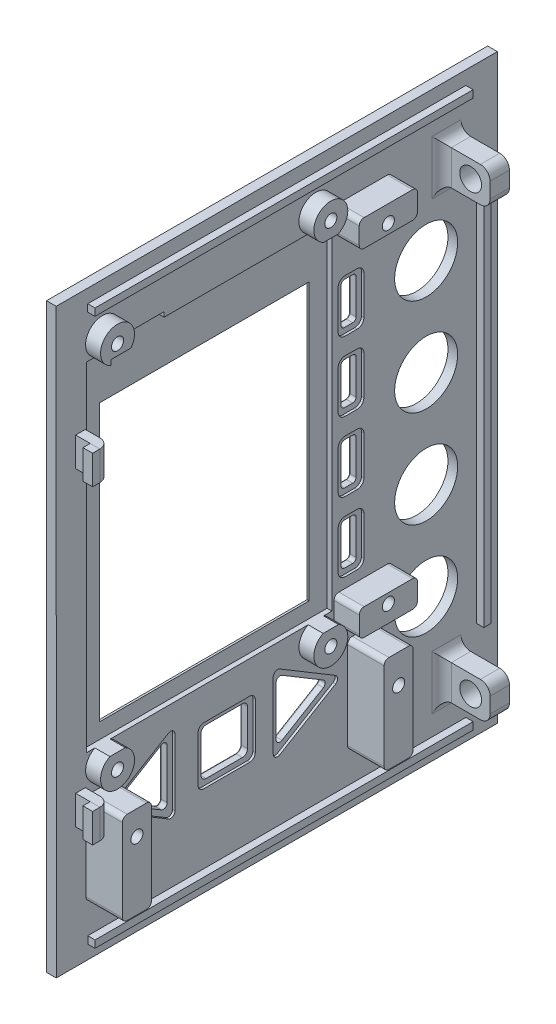
SolidWorks part; units mm, degrees
ref_plane "Front Plane" through (0, 0, 0) normal (0, 0, 1) x (1, 0, 0)
ref_plane "Top Plane" through (0, 0, 0) normal (0, 1, 0) x (1, 0, 0)
ref_plane "Right Plane" through (0, 0, 0) normal (1, 0, 0) x (0, 0, -1)
ref_plane "Plane2" through (-1175.048, -0.0877, 0) normal (-1, -0.0001, 0) x (0, 0, 1)
sketch "Sketch2" plane through (-1175.048, -0.0877, 0) normal (-1, -0.0001, 0) x (0, 0, 1)
  line L0 (-1289.195, -889.282) -> (-1289.195, -789.282) construction
  line L1 (-1204.195, -779.282) -> (-1295.195, -779.282)
  line L2 (-1204.195, -779.282) -> (-1204.195, -899.282)
  line L3 (-1204.195, -899.282) -> (-1295.195, -899.282)
  line L4 (-1295.195, -779.282) -> (-1295.195, -899.282)
  line L5 (-1289.195, -889.282) -> (-1287.685, -889.282) construction
  line L6 (-1289.195, -789.282) -> (-1287.685, -789.282) construction
  circle A0 centre (-1280.5, -869.282) radius 6.5
  circle A1 centre (-1280.5, -849.282) radius 6.5
  circle A2 centre (-1280.5, -829.282) radius 6.5
  circle A3 centre (-1280.5, -809.282) radius 6.5
  ellipse E0 centre (-1280.5, -869.282) end of major axis (-1280.4976, -868.632) minor radius 0.65 construction
  ellipse E1 centre (-1280.5, -849.282) end of major axis (-1280.4976, -848.632) minor radius 0.65 construction
  ellipse E2 centre (-1280.5, -829.282) end of major axis (-1280.4976, -828.632) minor radius 0.65 construction
  ellipse E3 centre (-1280.5, -809.282) end of major axis (-1280.4976, -808.632) minor radius 0.65 construction
  ellipse E4 centre (-1280.5, -869.282) end of major axis (-1280.4976, -868.632) minor radius 0.65
  ellipse E5 centre (-1280.5, -849.282) end of major axis (-1280.4976, -848.632) minor radius 0.65 construction
  ellipse E6 centre (-1280.5, -829.282) end of major axis (-1280.4976, -828.632) minor radius 0.65
  ellipse E7 centre (-1280.5, -809.282) end of major axis (-1280.4976, -808.632) minor radius 0.65
  dimension "D5" = 13
  dimension "D6" = 13
  dimension "D7" = 13
  dimension "D8" = 13
  dimension "D1" = 6
  dimension "D2" = 10
  dimension "D3" = 10
  dimension "D4" = 91
extrude "Boss-Extrude2" add sketch "Sketch2" along normal blind 2 contours L1 L4 L3 L2 A3 A2 A1 A0 region at (-1174.9854, -839.3697, -1248.1207)
sketch "Sketch3" plane through (-1177.048, -0.0879, 0) normal (-1, -0.0001, 0) x (0, 0, 1)
  line L12 (-1214.15, -858.982) -> (-1257.35, -858.982) construction
  line L13 (-1257.35, -858.982) -> (-1257.35, -802.002) construction
  line L14 (-1214.15, -802.002) -> (-1214.15, -858.982) construction
  line L15 (-1257.35, -802.002) -> (-1214.15, -802.002) construction
  line L16 (-1214.15, -858.982) -> (-1257.35, -858.982)
  line L17 (-1257.35, -858.982) -> (-1257.35, -802.002)
  line L18 (-1214.15, -802.002) -> (-1214.15, -858.982)
  line L19 (-1257.35, -802.002) -> (-1214.15, -802.002)
extrude "tft_cutout" cut sketch "Sketch3" against normal through all
sketch "tft_inset_cutout" plane through (-1175.048, -0.0877, 0) normal (1, 0.0001, 0) x (0, 0, -1)
  line L4 (1210.95, -792.861) -> (1210.95, -861.661) construction
  line L5 (1260.55, -792.861) -> (1210.95, -792.861) construction
  line L12 (1260.55, -861.661) -> (1260.55, -792.861) construction
  line L17 (1210.95, -861.661) -> (1260.55, -861.661) construction
  line L18 (1260.55, -861.661) -> (1260.55, -792.861) construction
  line L19 (1210.95, -861.661) -> (1260.55, -861.661) construction
  line L20 (1210.95, -792.861) -> (1210.95, -861.661) construction
  line L21 (1260.55, -792.861) -> (1210.95, -792.861) construction
  line L22 (1261.05, -792.361) -> (1210.45, -792.361)
  line L26 (1212.45, -792.861) -> (1226.45, -792.861)
  line L27 (1212.45, -792.861) -> (1212.45, -791.361)
  line L28 (1212.45, -791.361) -> (1226.45, -791.361)
  line L29 (1226.45, -792.861) -> (1226.45, -791.361)
  line L30 (1210.45, -792.361) -> (1210.45, -862.161)
  line L31 (1210.45, -862.161) -> (1261.05, -862.161)
  line L32 (1261.05, -862.161) -> (1261.05, -792.361)
  line M40 (1257.35, -858.982) -> (1214.15, -858.982)
  line M41 (1214.15, -858.982) -> (1214.15, -802.002)
  line M42 (1214.15, -802.002) -> (1257.35, -802.002)
  line M43 (1257.35, -802.002) -> (1257.35, -858.982)
  dimension "D3" = 1.5
  dimension "D4" = 0.5
  dimension "D1" = 14
  dimension "D2" = 1.5
extrude "Cut-Extrude2" cut sketch "tft_inset_cutout" against normal up to surface (1 mm away) contours L18 | L31 L32 L22 L29 L26 L27 L30 M43 M40 M41 M42 | L26 L29 L22 L27 | L22 L29 L28 L27 region at (-1174.9863, -827.3487, -1260.1879) region at (-1174.9889, -792.6987, -1219.45) region at (-1174.9889, -791.9487, -1219.45)
chamfer "Chamfer2" distance 1 angle 30 4 edges at (-1176.986, -830.5798, -1257.35) (-1176.9839, -859.0698, -1235.75) (-1176.986, -830.5798, -1214.15) (-1176.9882, -802.0898, -1235.75) first distance on face at (-1176.986, -830.5798, -1235.75)
sketch "Sketch6" plane through (-1175.048, -0.0877, 0) normal (1, 0.0001, 0) x (0, 0, -1)
  line L5 (1261.5, -864.9905) -> (1273.5, -864.9905)
  line L6 (1261.5, -864.9905) -> (1261.5, -859.4905)
  line L7 (1261.5, -859.4905) -> (1273.5, -859.4905)
  line L8 (1261.5, -864.9905) -> (1273.5, -864.9905)
  line L9 (1273.5, -864.9905) -> (1273.5, -789.9905)
  line L10 (1273.5, -789.9905) -> (1261.5, -789.9905)
  line L11 (1261.5, -789.9905) -> (1261.5, -864.9905)
  line L12 (1261.5, -864.9905) -> (1273.5, -864.9905) construction
  line L13 (1273.5, -864.9905) -> (1273.5, -789.9905) construction
  line L14 (1273.5, -789.9905) -> (1261.5, -789.9905) construction
  line L15 (1261.5, -789.9905) -> (1261.5, -864.9905) construction
  line L16 (1273.5, -864.9905) -> (1273.5, -859.4905)
  line L17 (1261.5, -789.9905) -> (1273.5, -789.9905)
  line L18 (1261.5, -789.9905) -> (1261.5, -795.4905)
  line L19 (1261.5, -795.4905) -> (1273.5, -795.4905)
  line L20 (1273.5, -789.9905) -> (1273.5, -795.4905)
  circle A0 centre (1267.5, -861.4905) radius 1.25 construction
  circle A1 centre (1267.5, -861.4905) radius 1.25 construction
  circle A2 centre (1267.5, -861.4905) radius 1.25
  circle A3 centre (1267.5, -793.4905) radius 1.25 construction
  circle A4 centre (1267.5, -793.4905) radius 1.25 construction
  circle A5 centre (1267.5, -793.4905) radius 1.25
  dimension "D2" = 2.5
  dimension "D4" = 2.5
  dimension "D3" = 2
  dimension "D5" = 2
extrude "menu_standoffs" add sketch "Sketch6" along normal up to surface (5.203 mm away)
fillet "Fillet1" radius 1 8 edges at (-1172.3871, -795.578, -1261.5) (-1172.3871, -795.578, -1273.5) (-1172.3875, -790.078, -1273.5) (-1172.3875, -790.078, -1261.5) (-1172.3824, -859.578, -1273.5) (-1172.3824, -859.578, -1261.5) (-1172.382, -865.078, -1261.5) (-1172.382, -865.078, -1273.5)
sketch "Sketch7" plane through (-1169.845, -0.0873, 0) normal (1, 0.0001, 0) x (0, 0, -1)
  circle A0 centre (1267.5, -861.4905) radius 1.25 construction
  circle A1 centre (1267.5, -793.4905) radius 1.25 construction
  circle A2 centre (1267.5, -861.4905) radius 1.25
  circle A3 centre (1267.5, -793.4905) radius 1.25
extrude "menu_standoff_holes" [suppressed] cut sketch "Sketch7" against normal blind 5 contours A2
sketch "Sketch8" plane through (-1175.048, -0.0877, 0) normal (1, 0.0001, 0) x (0, 0, -1)
  circle A0 centre (1213.75, -865.282) radius 1.55 construction
  circle A1 centre (1257.75, -865.282) radius 1.55 construction
  circle A2 centre (1257.75, -789.202) radius 1.55 construction
  circle A3 centre (1213.75, -789.2023) radius 1.55 construction
  circle A4 centre (1213.75, -865.282) radius 1.55 construction
  circle A5 centre (1257.75, -865.282) radius 1.55 construction
  circle A6 centre (1257.75, -789.202) radius 1.55 construction
  circle A7 centre (1213.75, -789.2023) radius 1.55 construction
  circle A8 centre (1213.75, -789.2023) radius 3.5
  circle A9 centre (1257.75, -789.202) radius 3.5
  circle A10 centre (1257.75, -865.282) radius 3.5
  circle A11 centre (1213.75, -865.282) radius 3.5
  circle A12 centre (1213.75, -789.2023) radius 1.25
  circle A13 centre (1213.75, -865.282) radius 1.25
  circle A14 centre (1257.75, -865.282) radius 1.25
  circle A15 centre (1257.75, -789.202) radius 1.25
  dimension "D2" = 2.5
  dimension "D1" = 7
extrude "TFT_standoffs" add sketch "Sketch8" along normal up to surface (3.09 mm away)
sketch "Sketch9" plane through (-1175.048, -0.0877, 0) normal (1, 0.0001, 0) x (0, 0, -1)
  circle A0 centre (1213.75, -789.2023) radius 1.25 construction
  circle A1 centre (1213.75, -865.282) radius 1.25 construction
  circle A2 centre (1257.75, -865.282) radius 1.25 construction
  circle A3 centre (1257.75, -789.202) radius 1.25 construction
  circle A4 centre (1213.75, -789.2023) radius 1.25
  circle A5 centre (1213.75, -865.282) radius 1.25
  circle A6 centre (1257.75, -865.282) radius 1.25
  circle A7 centre (1257.75, -789.202) radius 1.25
extrude "TFT_standoff_holes" cut sketch "Sketch9" against normal offset from surface (1 mm away) 1 up to face at (-1176.986, -830.5798, -1235.75)
extrude "Cut-Extrude5" cut sketch "Sketch5<3>" along normal through all contours L31 L32 L22 L29 L26 L27 L30 M43 M40 M41 M42 | L22 L29 L28 L27 | L26 L29 L22 L27 region at (-1174.9863, -827.3487, -1260.1879) region at (-1174.9889, -792.6987, -1219.45) region at (-1174.9889, -791.9487, -1219.45)
sketch "Sketch5<3>" plane through (-1175.048, -0.0877, 0) normal (1, 0.0001, 0) x (0, 0, -1) same geometry as "tft_inset_cutout"
sketch "Sketch10" plane through (-1175.048, -0.0877, 0) normal (1, 0.0001, 0) x (0, 0, -1)
  line L0 (1267.2535, -804.997) -> (1267.2535, -812.997) construction
  line L1 (1266.2535, -813.997) -> (1263.7535, -813.997) construction
  line L2 (1262.7535, -812.997) -> (1262.7535, -804.997) construction
  line L3 (1263.7535, -803.997) -> (1266.2535, -803.997) construction
  line L4 (1267.2535, -804.997) -> (1267.2535, -812.997) construction
  line L5 (1266.2535, -813.997) -> (1263.7535, -813.997) construction
  line L6 (1262.7535, -812.997) -> (1262.7535, -804.997) construction
  line L7 (1263.7535, -803.997) -> (1266.2535, -803.997) construction
  line L8 (1267.6535, -804.997) -> (1267.6535, -812.997)
  line L9 (1266.2535, -814.397) -> (1263.7535, -814.397)
  line L10 (1262.3535, -812.997) -> (1262.3535, -804.997)
  line L11 (1263.7535, -803.597) -> (1266.2535, -803.597)
  line L12 (1267.6535, -819.327) -> (1267.6535, -827.327)
  line L13 (1266.2535, -828.727) -> (1263.7535, -828.727)
  line L14 (1262.3535, -827.327) -> (1262.3535, -819.327)
  line L15 (1263.7535, -817.927) -> (1266.2535, -817.927)
  line L16 (1267.2535, -819.327) -> (1267.2535, -827.327) construction
  line L17 (1266.2535, -828.327) -> (1263.7535, -828.327) construction
  line L18 (1262.7535, -827.327) -> (1262.7535, -819.327) construction
  line L19 (1263.7535, -818.327) -> (1266.2535, -818.327) construction
  line L20 (1267.6535, -833.657) -> (1267.6535, -841.657)
  line L21 (1266.2535, -843.057) -> (1263.7535, -843.057)
  line L22 (1262.3535, -841.657) -> (1262.3535, -833.657)
  line L23 (1263.7535, -832.257) -> (1266.2535, -832.257)
  line L24 (1267.2535, -833.657) -> (1267.2535, -841.657) construction
  line L25 (1266.2535, -842.657) -> (1263.7535, -842.657) construction
  line L26 (1262.7535, -841.657) -> (1262.7535, -833.657) construction
  line L27 (1263.7535, -832.657) -> (1266.2535, -832.657) construction
  line L28 (1267.6535, -847.987) -> (1267.6535, -855.987)
  line L29 (1266.2535, -857.387) -> (1263.7535, -857.387)
  line L30 (1262.3535, -855.987) -> (1262.3535, -847.987)
  line L31 (1263.7535, -846.587) -> (1266.2535, -846.587)
  line L32 (1267.2535, -847.987) -> (1267.2535, -855.987) construction
  line L33 (1266.2535, -856.987) -> (1263.7535, -856.987) construction
  line L34 (1262.7535, -855.987) -> (1262.7535, -847.987) construction
  line L35 (1263.7535, -846.987) -> (1266.2535, -846.987) construction
  arc A0 (1267.2535, -804.997) -> (1266.2535, -803.997) centre (1266.2535, -804.997) ccw construction
  arc A1 (1266.2535, -813.997) -> (1267.2535, -812.997) centre (1266.2535, -812.997) ccw construction
  arc A2 (1262.7535, -812.997) -> (1263.7535, -813.997) centre (1263.7535, -812.997) ccw construction
  arc A3 (1263.7535, -803.997) -> (1262.7535, -804.997) centre (1263.7535, -804.997) ccw construction
  arc A4 (1267.2535, -804.997) -> (1266.2535, -803.997) centre (1266.2535, -804.997) ccw construction
  arc A5 (1266.2535, -813.997) -> (1267.2535, -812.997) centre (1266.2535, -812.997) ccw construction
  arc A6 (1262.7535, -812.997) -> (1263.7535, -813.997) centre (1263.7535, -812.997) ccw construction
  arc A7 (1263.7535, -803.997) -> (1262.7535, -804.997) centre (1263.7535, -804.997) ccw construction
  arc A8 (1266.2535, -814.397) -> (1267.6535, -812.997) centre (1266.2535, -812.997) ccw
  arc A9 (1262.3535, -812.997) -> (1263.7535, -814.397) centre (1263.7535, -812.997) ccw
  arc A10 (1263.7535, -803.597) -> (1262.3535, -804.997) centre (1263.7535, -804.997) ccw
  arc A11 (1267.6535, -804.997) -> (1266.2535, -803.597) centre (1266.2535, -804.997) ccw
  arc A12 (1266.2535, -828.727) -> (1267.6535, -827.327) centre (1266.2535, -827.327) ccw
  arc A13 (1262.3535, -827.327) -> (1263.7535, -828.727) centre (1263.7535, -827.327) ccw
  arc A14 (1263.7535, -817.927) -> (1262.3535, -819.327) centre (1263.7535, -819.327) ccw
  arc A15 (1267.6535, -819.327) -> (1266.2535, -817.927) centre (1266.2535, -819.327) ccw
  arc A16 (1267.2535, -819.327) -> (1266.2535, -818.327) centre (1266.2535, -819.327) ccw construction
  arc A17 (1266.2535, -828.327) -> (1267.2535, -827.327) centre (1266.2535, -827.327) ccw construction
  arc A18 (1262.7535, -827.327) -> (1263.7535, -828.327) centre (1263.7535, -827.327) ccw construction
  arc A19 (1263.7535, -818.327) -> (1262.7535, -819.327) centre (1263.7535, -819.327) ccw construction
  arc A20 (1266.2535, -843.057) -> (1267.6535, -841.657) centre (1266.2535, -841.657) ccw
  arc A21 (1262.3535, -841.657) -> (1263.7535, -843.057) centre (1263.7535, -841.657) ccw
  arc A22 (1263.7535, -832.257) -> (1262.3535, -833.657) centre (1263.7535, -833.657) ccw
  arc A23 (1267.6535, -833.657) -> (1266.2535, -832.257) centre (1266.2535, -833.657) ccw
  arc A24 (1267.2535, -833.657) -> (1266.2535, -832.657) centre (1266.2535, -833.657) ccw construction
  arc A25 (1266.2535, -842.657) -> (1267.2535, -841.657) centre (1266.2535, -841.657) ccw construction
  arc A26 (1262.7535, -841.657) -> (1263.7535, -842.657) centre (1263.7535, -841.657) ccw construction
  arc A27 (1263.7535, -832.657) -> (1262.7535, -833.657) centre (1263.7535, -833.657) ccw construction
  arc A28 (1266.2535, -857.387) -> (1267.6535, -855.987) centre (1266.2535, -855.987) ccw
  arc A29 (1262.3535, -855.987) -> (1263.7535, -857.387) centre (1263.7535, -855.987) ccw
  arc A30 (1263.7535, -846.587) -> (1262.3535, -847.987) centre (1263.7535, -847.987) ccw
  arc A31 (1267.6535, -847.987) -> (1266.2535, -846.587) centre (1266.2535, -847.987) ccw
  arc A32 (1267.2535, -847.987) -> (1266.2535, -846.987) centre (1266.2535, -847.987) ccw construction
  arc A33 (1266.2535, -856.987) -> (1267.2535, -855.987) centre (1266.2535, -855.987) ccw construction
  arc A34 (1262.7535, -855.987) -> (1263.7535, -856.987) centre (1263.7535, -855.987) ccw construction
  arc A35 (1263.7535, -846.987) -> (1262.7535, -847.987) centre (1263.7535, -847.987) ccw construction
  dimension "D1" = 0.4
  dimension "D2" = 4
extrude "menu_panel_inset" cut sketch "Sketch10" against normal offset from surface 1.5 and the other way through all up to face at (-1176.986, -830.5798, -1235.75)
sketch "Sketch11" plane through (-1177.048, -0.0879, 0) normal (-1, -0.0001, 0) x (0, 0, 1)
  line L0 (-1265.8535, -812.997) -> (-1264.1535, -812.997) construction
  line L1 (-1266.2535, -805.397) -> (-1266.2535, -812.597) construction
  line L2 (-1265.8535, -804.997) -> (-1264.1535, -804.997) construction
  line L3 (-1263.7535, -805.397) -> (-1263.7535, -812.597) construction
  line L4 (-1265.8535, -812.997) -> (-1264.1535, -812.997) construction
  line L5 (-1266.2535, -805.397) -> (-1266.2535, -812.597) construction
  line L6 (-1265.8535, -804.997) -> (-1264.1535, -804.997) construction
  line L7 (-1263.7535, -805.397) -> (-1263.7535, -812.597) construction
  line L8 (-1263.4535, -805.397) -> (-1263.4535, -812.597)
  line L9 (-1265.8535, -813.297) -> (-1264.1535, -813.297)
  line L10 (-1266.5535, -805.397) -> (-1266.5535, -812.597)
  line L11 (-1265.8535, -804.697) -> (-1264.1535, -804.697)
  line L12 (-1263.4535, -819.727) -> (-1263.4535, -826.927)
  line L13 (-1265.8535, -827.627) -> (-1264.1535, -827.627)
  line L14 (-1266.5535, -819.727) -> (-1266.5535, -826.927)
  line L15 (-1265.8535, -819.027) -> (-1264.1535, -819.027)
  line L16 (-1265.8535, -827.327) -> (-1264.1535, -827.327) construction
  line L17 (-1266.2535, -819.727) -> (-1266.2535, -826.927) construction
  line L18 (-1265.8535, -819.327) -> (-1264.1535, -819.327) construction
  line L19 (-1263.7535, -819.727) -> (-1263.7535, -826.927) construction
  line L20 (-1263.4535, -834.057) -> (-1263.4535, -841.257)
  line L21 (-1265.8535, -841.957) -> (-1264.1535, -841.957)
  line L22 (-1266.5535, -834.057) -> (-1266.5535, -841.257)
  line L23 (-1265.8535, -833.357) -> (-1264.1535, -833.357)
  line L24 (-1265.8535, -841.657) -> (-1264.1535, -841.657) construction
  line L25 (-1266.2535, -834.057) -> (-1266.2535, -841.257) construction
  line L26 (-1265.8535, -833.657) -> (-1264.1535, -833.657) construction
  line L27 (-1263.7535, -834.057) -> (-1263.7535, -841.257) construction
  line L28 (-1263.4535, -848.387) -> (-1263.4535, -855.587)
  line L29 (-1265.8535, -856.287) -> (-1264.1535, -856.287)
  line L30 (-1266.5535, -848.387) -> (-1266.5535, -855.587)
  line L31 (-1265.8535, -847.687) -> (-1264.1535, -847.687)
  line L32 (-1265.8535, -855.987) -> (-1264.1535, -855.987) construction
  line L33 (-1266.2535, -848.387) -> (-1266.2535, -855.587) construction
  line L34 (-1265.8535, -847.987) -> (-1264.1535, -847.987) construction
  line L35 (-1263.7535, -848.387) -> (-1263.7535, -855.587) construction
  arc A0 (-1264.1535, -812.997) -> (-1263.7535, -812.597) centre (-1264.1535, -812.597) ccw construction
  arc A1 (-1266.2535, -812.597) -> (-1265.8535, -812.997) centre (-1265.8535, -812.597) ccw construction
  arc A2 (-1265.8535, -804.997) -> (-1266.2535, -805.397) centre (-1265.8535, -805.397) ccw construction
  arc A3 (-1263.7535, -805.397) -> (-1264.1535, -804.997) centre (-1264.1535, -805.397) ccw construction
  arc A4 (-1264.1535, -812.997) -> (-1263.7535, -812.597) centre (-1264.1535, -812.597) ccw construction
  arc A5 (-1266.2535, -812.597) -> (-1265.8535, -812.997) centre (-1265.8535, -812.597) ccw construction
  arc A6 (-1265.8535, -804.997) -> (-1266.2535, -805.397) centre (-1265.8535, -805.397) ccw construction
  arc A7 (-1263.7535, -805.397) -> (-1264.1535, -804.997) centre (-1264.1535, -805.397) ccw construction
  arc A8 (-1264.1535, -813.297) -> (-1263.4535, -812.597) centre (-1264.1535, -812.597) ccw
  arc A9 (-1266.5535, -812.597) -> (-1265.8535, -813.297) centre (-1265.8535, -812.597) ccw
  arc A10 (-1265.8535, -804.697) -> (-1266.5535, -805.397) centre (-1265.8535, -805.397) ccw
  arc A11 (-1263.4535, -805.397) -> (-1264.1535, -804.697) centre (-1264.1535, -805.397) ccw
  arc A12 (-1264.1535, -827.627) -> (-1263.4535, -826.927) centre (-1264.1535, -826.927) ccw
  arc A13 (-1266.5535, -826.927) -> (-1265.8535, -827.627) centre (-1265.8535, -826.927) ccw
  arc A14 (-1265.8535, -819.027) -> (-1266.5535, -819.727) centre (-1265.8535, -819.727) ccw
  arc A15 (-1263.4535, -819.727) -> (-1264.1535, -819.027) centre (-1264.1535, -819.727) ccw
  arc A16 (-1264.1535, -827.327) -> (-1263.7535, -826.927) centre (-1264.1535, -826.927) ccw construction
  arc A17 (-1266.2535, -826.927) -> (-1265.8535, -827.327) centre (-1265.8535, -826.927) ccw construction
  arc A18 (-1265.8535, -819.327) -> (-1266.2535, -819.727) centre (-1265.8535, -819.727) ccw construction
  arc A19 (-1263.7535, -819.727) -> (-1264.1535, -819.327) centre (-1264.1535, -819.727) ccw construction
  arc A20 (-1264.1535, -841.957) -> (-1263.4535, -841.257) centre (-1264.1535, -841.257) ccw
  arc A21 (-1266.5535, -841.257) -> (-1265.8535, -841.957) centre (-1265.8535, -841.257) ccw
  arc A22 (-1265.8535, -833.357) -> (-1266.5535, -834.057) centre (-1265.8535, -834.057) ccw
  arc A23 (-1263.4535, -834.057) -> (-1264.1535, -833.357) centre (-1264.1535, -834.057) ccw
  arc A24 (-1264.1535, -841.657) -> (-1263.7535, -841.257) centre (-1264.1535, -841.257) ccw construction
  arc A25 (-1266.2535, -841.257) -> (-1265.8535, -841.657) centre (-1265.8535, -841.257) ccw construction
  arc A26 (-1265.8535, -833.657) -> (-1266.2535, -834.057) centre (-1265.8535, -834.057) ccw construction
  arc A27 (-1263.7535, -834.057) -> (-1264.1535, -833.657) centre (-1264.1535, -834.057) ccw construction
  arc A28 (-1264.1535, -856.287) -> (-1263.4535, -855.587) centre (-1264.1535, -855.587) ccw
  arc A29 (-1266.5535, -855.587) -> (-1265.8535, -856.287) centre (-1265.8535, -855.587) ccw
  arc A30 (-1265.8535, -847.687) -> (-1266.5535, -848.387) centre (-1265.8535, -848.387) ccw
  arc A31 (-1263.4535, -848.387) -> (-1264.1535, -847.687) centre (-1264.1535, -848.387) ccw
  arc A32 (-1264.1535, -855.987) -> (-1263.7535, -855.587) centre (-1264.1535, -855.587) ccw construction
  arc A33 (-1266.2535, -855.587) -> (-1265.8535, -855.987) centre (-1265.8535, -855.587) ccw construction
  arc A34 (-1265.8535, -847.987) -> (-1266.2535, -848.387) centre (-1265.8535, -848.387) ccw construction
  arc A35 (-1263.7535, -848.387) -> (-1264.1535, -847.987) centre (-1264.1535, -848.387) ccw construction
  dimension "D1" = 0.3
  dimension "D2" = 4
extrude "menu_panel_cutout" cut sketch "Sketch11" against normal through all
fillet "Fillet2" radius 0.25 32 edges at (-1176.9876, -809.0848, -1263.4535) (-1176.9873, -813.1798, -1263.6586) (-1176.9873, -813.3848, -1265.0035) (-1176.9873, -813.1798, -1266.3485) (-1176.9876, -809.0848, -1266.5535) (-1176.9879, -804.9899, -1266.3485) (-1176.988, -804.7848, -1265.0035) (-1176.9862, -827.7148, -1265.0035) (-1176.9863, -827.5098, -1266.3485) (-1176.9866, -823.4148, -1266.5535) (-1176.9869, -819.3199, -1266.3485) (-1176.9869, -819.1148, -1265.0035) (-1176.9869, -819.3199, -1263.6586) (-1176.9866, -823.4148, -1263.4535) (-1176.9852, -842.0448, -1265.0035) (-1176.9852, -841.8398, -1266.3485) (-1176.9855, -837.7448, -1266.5535) (-1176.9858, -833.6499, -1266.3485) (-1176.9858, -833.4448, -1265.0035) (-1176.9858, -833.6499, -1263.6586) (-1176.9855, -837.7448, -1263.4535) (-1176.9844, -852.0748, -1263.4535) (-1176.9841, -856.1698, -1263.6586) (-1176.9841, -856.3748, -1265.0035) (-1176.9841, -856.1698, -1266.3485) (-1176.9844, -852.0748, -1266.5535) (-1176.9847, -847.9799, -1266.3485) (-1176.9847, -847.7748, -1265.0035) (-1176.9879, -804.9899, -1263.6586) (-1176.9863, -827.5098, -1263.6586) (-1176.9852, -841.8398, -1263.6586) (-1176.9847, -847.9799, -1263.6586)
sketch "Sketch12" plane through (-1175.048, -0.0877, 0) normal (1, 0.0001, 0) x (0, 0, -1)
  line L0 (1270.2797, -888.782) -> (1210.2797, -888.782) construction
  line L1 (1270.2797, -868.782) -> (1264.2797, -868.782)
  line L2 (1270.2797, -868.782) -> (1270.2797, -888.782)
  line L3 (1270.2797, -888.782) -> (1264.2797, -888.782)
  line L4 (1264.2797, -868.782) -> (1264.2797, -888.782)
  line L6 (1210.2797, -888.782) -> (1216.2797, -888.782)
  line L7 (1210.2797, -888.782) -> (1210.2797, -869.782)
  line L8 (1210.2797, -869.782) -> (1216.2797, -869.782)
  line L9 (1216.2797, -888.782) -> (1216.2797, -869.782)
  line L10 (1210.2797, -868.782) -> (1270.2797, -868.782) construction
  circle A0 centre (1267.2797, -874.782) radius 1.25
  circle A1 centre (1213.2797, -874.782) radius 1.25
  dimension "D1" = 6
  dimension "D2" = 2.5
  dimension "D4" = 2.5
  dimension "D3" = 6
  dimension "D5" = 1
extrude "selector_standoffs" add sketch "Sketch12" along normal up to surface (7.55 mm away) contours L6 L9 L8 L7 A1 | L1 L4 L3 L2 A0 region at (-1174.9824, -879.0403, -1267.2797) region at (-1174.9824, -879.5722, -1213.2797)
fillet "Fillet3" radius 1 8 edges at (-1171.2067, -888.8694, -1270.2797) (-1171.2082, -868.8694, -1270.2797) (-1171.2082, -868.8694, -1264.2797) (-1171.2067, -888.8694, -1264.2797) (-1171.2067, -888.8694, -1216.2797) (-1171.2067, -888.8694, -1210.2797) (-1171.2081, -869.8694, -1210.2797) (-1171.2081, -869.8694, -1216.2797)
sketch "Sketch13" plane through (-1175.048, -0.0877, 0) normal (1, 0.0001, 0) x (0, 0, -1)
  line L0 (1218.0014, -875.2178) -> (1226.5296, -880.3347) construction
  line L1 (1227.2868, -879.906) -> (1227.2868, -869.6722) construction
  line L2 (1226.5296, -869.2434) -> (1218.0014, -874.3603) construction
  line L3 (1234.85, -871.0391) -> (1234.85, -878.5391) construction
  line L4 (1235.6, -879.2891) -> (1243.1, -879.2891) construction
  line L5 (1243.1, -870.2891) -> (1235.6, -870.2891) construction
  line L6 (1243.85, -878.5391) -> (1243.85, -871.0391) construction
  line L7 (1259.6354, -874.3603) -> (1251.1072, -869.2434) construction
  line L8 (1250.35, -869.6722) -> (1250.35, -879.906) construction
  line L9 (1251.1072, -880.3347) -> (1259.6354, -875.2178) construction
  line L10 (1218.0014, -875.2178) -> (1226.5296, -880.3347) construction
  line L11 (1227.2868, -879.906) -> (1227.2868, -869.6722) construction
  line L12 (1226.5296, -869.2434) -> (1218.0014, -874.3603) construction
  line L13 (1234.85, -871.0391) -> (1234.85, -878.5391) construction
  line L14 (1235.6, -879.2891) -> (1243.1, -879.2891) construction
  line L15 (1243.1, -870.2891) -> (1235.6, -870.2891) construction
  line L16 (1243.85, -878.5391) -> (1243.85, -871.0391) construction
  line L17 (1259.6354, -874.3603) -> (1251.1072, -869.2434) construction
  line L18 (1250.35, -869.6722) -> (1250.35, -879.906) construction
  line L19 (1251.1072, -880.3347) -> (1259.6354, -875.2178) construction
  line L20 (1217.847, -875.4751) -> (1226.3752, -880.592)
  line L21 (1227.5868, -879.906) -> (1227.5868, -869.6722)
  line L22 (1226.3752, -868.9862) -> (1217.847, -874.1031)
  line L23 (1234.55, -871.0391) -> (1234.55, -878.5391)
  line L24 (1235.6, -879.5891) -> (1243.1, -879.5891)
  line L25 (1244.15, -878.5391) -> (1244.15, -871.0391)
  line L26 (1243.1, -869.9891) -> (1235.6, -869.9891)
  line L27 (1259.7898, -874.1031) -> (1251.2616, -868.9862)
  line L28 (1250.05, -869.6722) -> (1250.05, -879.906)
  line L29 (1251.2616, -880.592) -> (1259.7898, -875.4751)
  arc A0 (1218.0014, -874.3603) -> (1218.0014, -875.2178) centre (1218.2586, -874.7891) ccw construction
  arc A1 (1226.5296, -880.3347) -> (1227.2868, -879.906) centre (1226.7868, -879.906) ccw construction
  arc A2 (1227.2868, -869.6722) -> (1226.5296, -869.2434) centre (1226.7868, -869.6722) ccw construction
  arc A3 (1235.6, -870.2891) -> (1234.85, -871.0391) centre (1235.6, -871.0391) ccw construction
  arc A4 (1234.85, -878.5391) -> (1235.6, -879.2891) centre (1235.6, -878.5391) ccw construction
  arc A5 (1243.1, -879.2891) -> (1243.85, -878.5391) centre (1243.1, -878.5391) ccw construction
  arc A6 (1243.85, -871.0391) -> (1243.1, -870.2891) centre (1243.1, -871.0391) ccw construction
  arc A7 (1259.6354, -875.2178) -> (1259.6354, -874.3603) centre (1259.3782, -874.7891) ccw construction
  arc A8 (1251.1072, -869.2434) -> (1250.35, -869.6722) centre (1250.85, -869.6722) ccw construction
  arc A9 (1250.35, -879.906) -> (1251.1072, -880.3347) centre (1250.85, -879.906) ccw construction
  arc A10 (1218.0014, -874.3603) -> (1218.0014, -875.2178) centre (1218.2586, -874.7891) ccw construction
  arc A11 (1226.5296, -880.3347) -> (1227.2868, -879.906) centre (1226.7868, -879.906) ccw construction
  arc A12 (1227.2868, -869.6722) -> (1226.5296, -869.2434) centre (1226.7868, -869.6722) ccw construction
  arc A13 (1235.6, -870.2891) -> (1234.85, -871.0391) centre (1235.6, -871.0391) ccw construction
  arc A14 (1234.85, -878.5391) -> (1235.6, -879.2891) centre (1235.6, -878.5391) ccw construction
  arc A15 (1243.1, -879.2891) -> (1243.85, -878.5391) centre (1243.1, -878.5391) ccw construction
  arc A16 (1243.85, -871.0391) -> (1243.1, -870.2891) centre (1243.1, -871.0391) ccw construction
  arc A17 (1259.6354, -875.2178) -> (1259.6354, -874.3603) centre (1259.3782, -874.7891) ccw construction
  arc A18 (1251.1072, -869.2434) -> (1250.35, -869.6722) centre (1250.85, -869.6722) ccw construction
  arc A19 (1250.35, -879.906) -> (1251.1072, -880.3347) centre (1250.85, -879.906) ccw construction
  arc A20 (1226.3752, -880.592) -> (1227.5868, -879.906) centre (1226.7868, -879.906) ccw
  arc A21 (1227.5868, -869.6722) -> (1226.3752, -868.9862) centre (1226.7868, -869.6722) ccw
  arc A22 (1217.847, -874.1031) -> (1217.847, -875.4751) centre (1218.2586, -874.7891) ccw
  arc A23 (1234.55, -878.5391) -> (1235.6, -879.5891) centre (1235.6, -878.5391) ccw
  arc A24 (1243.1, -879.5891) -> (1244.15, -878.5391) centre (1243.1, -878.5391) ccw
  arc A25 (1244.15, -871.0391) -> (1243.1, -869.9891) centre (1243.1, -871.0391) ccw
  arc A26 (1235.6, -869.9891) -> (1234.55, -871.0391) centre (1235.6, -871.0391) ccw
  arc A27 (1251.2616, -868.9862) -> (1250.05, -869.6722) centre (1250.85, -869.6722) ccw
  arc A28 (1250.05, -879.906) -> (1251.2616, -880.592) centre (1250.85, -879.906) ccw
  arc A29 (1259.7898, -875.4751) -> (1259.7898, -874.1031) centre (1259.3782, -874.7891) ccw
  dimension "D1" = 0.3
  dimension "D2" = 0.3
  dimension "D3" = 0.3
extrude "selector_cutout" cut sketch "Sketch13" against normal through all
fillet "Fillet4" radius 0.25 20 edges at (-1176.9824, -879.6769, -1239.35) (-1176.9824, -879.3694, -1234.8575) (-1176.9827, -874.8769, -1234.55) (-1176.9831, -870.3845, -1234.8575) (-1176.9831, -870.0769, -1239.35) (-1176.9831, -870.3845, -1243.8424) (-1176.9827, -874.8769, -1244.15) (-1176.9832, -869.0639, -1250.4558) (-1176.983, -871.6325, -1255.5257) (-1176.9827, -874.8769, -1260.1782) (-1176.9825, -878.1214, -1255.5257) (-1176.9823, -880.69, -1250.4558) (-1176.9824, -879.3694, -1243.8424) (-1176.9827, -874.8769, -1250.05) (-1176.9825, -878.1214, -1222.1111) (-1176.9827, -874.8769, -1217.4586) (-1176.983, -871.6325, -1222.1111) (-1176.9832, -869.0639, -1227.181) (-1176.9827, -874.8769, -1227.5868) (-1176.9823, -880.69, -1227.181)
sketch "Sketch17" plane through (-1175.048, -0.0877, 0) normal (1, 0.0001, 0) x (0, 0, -1)
  line L18 (1220.3082, -871.8101) -> (1216.0577, -874.3603) construction
  line L19 (1216.0577, -875.2178) -> (1220.3082, -877.7681) construction
  line L20 (1220.1868, -877.5537) -> (1220.1868, -872.0244) construction
  line L21 (1228.2868, -881.6722) -> (1228.2868, -867.906) construction
  line L22 (1227.5296, -867.4772) -> (1220.4505, -871.7247) construction
  line L23 (1220.5791, -871.6891) -> (1226.1368, -871.6891) construction
  line L24 (1226.3868, -871.9391) -> (1226.3868, -877.6391) construction
  line L25 (1226.1368, -877.8891) -> (1220.5791, -877.8891) construction
  line L26 (1220.4505, -877.8535) -> (1227.5296, -882.1009) construction
  line L27 (1220.3082, -871.8101) -> (1216.0577, -874.3603) construction
  line L28 (1216.0577, -875.2178) -> (1220.3082, -877.7681) construction
  line L29 (1220.1868, -877.5537) -> (1220.1868, -872.0244) construction
  line L30 (1228.2868, -881.6722) -> (1228.2868, -867.906) construction
  line L31 (1257.3286, -877.7681) -> (1261.5791, -875.2178) construction
  line L32 (1261.5791, -874.3603) -> (1257.3286, -871.8101) construction
  line L33 (1257.45, -872.0244) -> (1257.45, -877.5537) construction
  line L34 (1249.35, -867.906) -> (1249.35, -881.6722) construction
  line L35 (1250.1072, -882.1009) -> (1257.1863, -877.8535) construction
  line L36 (1257.0577, -877.8891) -> (1251.5, -877.8891) construction
  line L37 (1251.25, -877.6391) -> (1251.25, -871.9391) construction
  line L38 (1251.5, -871.6891) -> (1257.0577, -871.6891) construction
  line L39 (1257.1863, -871.7247) -> (1250.1072, -867.4772) construction
  line L40 (1233.85, -870.0391) -> (1233.85, -879.5391) construction
  line L41 (1234.6, -880.2891) -> (1244.1, -880.2891) construction
  line L42 (1244.85, -879.5391) -> (1244.85, -870.0391) construction
  line L43 (1244.1, -869.2891) -> (1234.6, -869.2891) construction
  line L44 (1257.3286, -877.7681) -> (1261.5791, -875.2178) construction
  line L45 (1261.5791, -874.3603) -> (1257.3286, -871.8101) construction
  line L46 (1257.45, -872.0244) -> (1257.45, -877.5537) construction
  line L47 (1249.35, -867.906) -> (1249.35, -881.6722) construction
  line L48 (1250.1072, -882.1009) -> (1257.1863, -877.8535) construction
  line L49 (1257.0577, -877.8891) -> (1251.5, -877.8891) construction
  line L50 (1251.25, -877.6391) -> (1251.25, -871.9391) construction
  line L51 (1251.5, -871.6891) -> (1257.0577, -871.6891) construction
  line L52 (1257.1863, -871.7247) -> (1250.1072, -867.4772) construction
  line L53 (1233.85, -870.0391) -> (1233.85, -879.5391) construction
  line L54 (1234.6, -880.2891) -> (1244.1, -880.2891) construction
  line L55 (1244.85, -879.5391) -> (1244.85, -870.0391) construction
  line L56 (1244.1, -869.2891) -> (1234.6, -869.2891) construction
  line L57 (1257.1863, -877.8535) -> (1257.3286, -877.7681)
  line L58 (1257.3286, -871.8101) -> (1257.1863, -871.7247)
  line L59 (1227.5296, -867.4772) -> (1220.4505, -871.7247) construction
  line L60 (1220.5791, -871.6891) -> (1226.1368, -871.6891) construction
  line L61 (1226.3868, -871.9391) -> (1226.3868, -877.6391) construction
  line L62 (1226.1368, -877.8891) -> (1220.5791, -877.8891) construction
  line L63 (1220.4505, -877.8535) -> (1227.5296, -882.1009) construction
  line L64 (1220.3082, -871.8101) -> (1220.4505, -871.7247)
  line L65 (1220.4505, -877.8535) -> (1220.3082, -877.7681)
  line L66 (1257.3921, -878.1965) -> (1257.5344, -878.1111)
  line L67 (1257.5344, -871.4671) -> (1257.3921, -871.3817)
  line L68 (1220.514, -872.1531) -> (1220.6563, -872.0677)
  line L69 (1220.6563, -877.5105) -> (1220.514, -877.4251)
  line L70 (1220.1024, -871.4671) -> (1215.8519, -874.0173)
  line L71 (1215.8519, -875.5608) -> (1220.1024, -878.1111)
  line L72 (1220.5868, -877.4811) -> (1220.5868, -872.0971)
  line L73 (1220.2447, -878.1965) -> (1227.3238, -882.4439)
  line L74 (1228.6868, -881.6722) -> (1228.6868, -867.906)
  line L75 (1227.3238, -867.1342) -> (1220.2447, -871.3817)
  line L76 (1257.5344, -878.1111) -> (1261.7849, -875.5608)
  line L77 (1261.7849, -874.0173) -> (1257.5344, -871.4671)
  line L78 (1257.05, -872.0971) -> (1257.05, -877.4811)
  line L79 (1257.3921, -871.3817) -> (1250.313, -867.1342)
  line L80 (1248.95, -867.906) -> (1248.95, -881.6722)
  line L81 (1250.313, -882.4439) -> (1257.3921, -878.1965)
  line L82 (1257.0213, -877.4891) -> (1251.65, -877.4891)
  line L83 (1251.65, -877.4891) -> (1251.65, -872.0891)
  line L84 (1251.65, -872.0891) -> (1257.0213, -872.0891)
  line L85 (1233.45, -870.0391) -> (1233.45, -879.5391)
  line L86 (1234.6, -880.6891) -> (1244.1, -880.6891)
  line L87 (1245.25, -879.5391) -> (1245.25, -870.0391)
  line L88 (1244.1, -868.8891) -> (1234.6, -868.8891)
  line L89 (1220.6155, -872.0891) -> (1225.9868, -872.0891)
  line L90 (1225.9868, -872.0891) -> (1225.9868, -877.4891)
  line L91 (1225.9868, -877.4891) -> (1220.6155, -877.4891)
  line L92 (1220.1024, -878.1111) -> (1220.2447, -878.1965)
  line L93 (1220.2447, -871.3817) -> (1220.1024, -871.4671)
  arc A18 (1216.0577, -874.3603) -> (1216.0577, -875.2178) centre (1216.315, -874.7891) ccw construction
  arc A19 (1220.1868, -877.5537) -> (1220.3082, -877.7681) centre (1220.4368, -877.5537) ccw construction
  arc A20 (1220.3082, -871.8101) -> (1220.1868, -872.0244) centre (1220.4368, -872.0244) ccw construction
  arc A21 (1228.2868, -867.906) -> (1227.5296, -867.4772) centre (1227.7868, -867.906) ccw construction
  arc A22 (1220.5791, -871.6891) -> (1220.4505, -871.7247) centre (1220.5791, -871.9391) ccw construction
  arc A23 (1226.3868, -871.9391) -> (1226.1368, -871.6891) centre (1226.1368, -871.9391) ccw construction
  arc A24 (1226.1368, -877.8891) -> (1226.3868, -877.6391) centre (1226.1368, -877.6391) ccw construction
  arc A25 (1220.4505, -877.8535) -> (1220.5791, -877.8891) centre (1220.5791, -877.6391) ccw construction
  arc A26 (1227.5296, -882.1009) -> (1228.2868, -881.6722) centre (1227.7868, -881.6722) ccw construction
  arc A27 (1261.5791, -875.2178) -> (1261.5791, -874.3603) centre (1261.3218, -874.7891) ccw construction
  arc A28 (1257.45, -872.0244) -> (1257.3286, -871.8101) centre (1257.2, -872.0244) ccw construction
  arc A29 (1257.3286, -877.7681) -> (1257.45, -877.5537) centre (1257.2, -877.5537) ccw construction
  arc A30 (1249.35, -881.6722) -> (1250.1072, -882.1009) centre (1249.85, -881.6722) ccw construction
  arc A31 (1257.0577, -877.8891) -> (1257.1863, -877.8535) centre (1257.0577, -877.6391) ccw construction
  arc A32 (1251.25, -877.6391) -> (1251.5, -877.8891) centre (1251.5, -877.6391) ccw construction
  arc A33 (1251.5, -871.6891) -> (1251.25, -871.9391) centre (1251.5, -871.9391) ccw construction
  arc A34 (1257.1863, -871.7247) -> (1257.0577, -871.6891) centre (1257.0577, -871.9391) ccw construction
  arc A35 (1250.1072, -867.4772) -> (1249.35, -867.906) centre (1249.85, -867.906) ccw construction
  arc A36 (1233.85, -879.5391) -> (1234.6, -880.2891) centre (1234.6, -879.5391) ccw construction
  arc A37 (1244.1, -880.2891) -> (1244.85, -879.5391) centre (1244.1, -879.5391) ccw construction
  arc A38 (1244.85, -870.0391) -> (1244.1, -869.2891) centre (1244.1, -870.0391) ccw construction
  arc A39 (1234.6, -869.2891) -> (1233.85, -870.0391) centre (1234.6, -870.0391) ccw construction
  arc A40 (1261.5791, -875.2178) -> (1261.5791, -874.3603) centre (1261.3218, -874.7891) ccw construction
  arc A41 (1257.45, -872.0244) -> (1257.3286, -871.8101) centre (1257.2, -872.0244) ccw construction
  arc A42 (1257.3286, -877.7681) -> (1257.45, -877.5537) centre (1257.2, -877.5537) ccw construction
  arc A43 (1249.35, -881.6722) -> (1250.1072, -882.1009) centre (1249.85, -881.6722) ccw construction
  arc A44 (1257.0577, -877.8891) -> (1257.1863, -877.8535) centre (1257.0577, -877.6391) ccw construction
  arc A45 (1251.25, -877.6391) -> (1251.5, -877.8891) centre (1251.5, -877.6391) ccw construction
  arc A46 (1251.5, -871.6891) -> (1251.25, -871.9391) centre (1251.5, -871.9391) ccw construction
  arc A47 (1257.1863, -871.7247) -> (1257.0577, -871.6891) centre (1257.0577, -871.9391) ccw construction
  arc A48 (1250.1072, -867.4772) -> (1249.35, -867.906) centre (1249.85, -867.906) ccw construction
  arc A49 (1233.85, -879.5391) -> (1234.6, -880.2891) centre (1234.6, -879.5391) ccw construction
  arc A50 (1244.1, -880.2891) -> (1244.85, -879.5391) centre (1244.1, -879.5391) ccw construction
  arc A51 (1244.85, -870.0391) -> (1244.1, -869.2891) centre (1244.1, -870.0391) ccw construction
  arc A52 (1234.6, -869.2891) -> (1233.85, -870.0391) centre (1234.6, -870.0391) ccw construction
  arc A53 (1216.0577, -874.3603) -> (1216.0577, -875.2178) centre (1216.315, -874.7891) ccw construction
  arc A54 (1220.1868, -877.5537) -> (1220.3082, -877.7681) centre (1220.4368, -877.5537) ccw construction
  arc A55 (1220.3082, -871.8101) -> (1220.1868, -872.0244) centre (1220.4368, -872.0244) ccw construction
  arc A56 (1228.2868, -867.906) -> (1227.5296, -867.4772) centre (1227.7868, -867.906) ccw construction
  arc A57 (1220.5791, -871.6891) -> (1220.4505, -871.7247) centre (1220.5791, -871.9391) ccw construction
  arc A58 (1226.3868, -871.9391) -> (1226.1368, -871.6891) centre (1226.1368, -871.9391) ccw construction
  arc A59 (1226.1368, -877.8891) -> (1226.3868, -877.6391) centre (1226.1368, -877.6391) ccw construction
  arc A60 (1220.4505, -877.8535) -> (1220.5791, -877.8891) centre (1220.5791, -877.6391) ccw construction
  arc A61 (1227.5296, -882.1009) -> (1228.2868, -881.6722) centre (1227.7868, -881.6722) ccw construction
  arc A62 (1215.8519, -874.0173) -> (1215.8519, -875.5608) centre (1216.315, -874.7891) ccw
  arc A63 (1220.5868, -877.4811) -> (1220.5868, -877.4811) centre (1220.5868, -877.4811) cw
  arc A64 (1220.5868, -872.0971) -> (1220.5868, -872.0971) centre (1220.5868, -872.0971) cw
  arc A65 (1227.3238, -882.4439) -> (1228.6868, -881.6722) centre (1227.7868, -881.6722) ccw
  arc A66 (1228.6868, -867.906) -> (1227.3238, -867.1342) centre (1227.7868, -867.906) ccw
  arc A67 (1261.7849, -875.5608) -> (1261.7849, -874.0173) centre (1261.3218, -874.7891) ccw
  arc A68 (1257.05, -872.0971) -> (1257.05, -872.0971) centre (1257.05, -872.0971) cw
  arc A69 (1257.05, -877.4811) -> (1257.05, -877.4811) centre (1257.05, -877.4811) cw
  arc A70 (1250.313, -867.1342) -> (1248.95, -867.906) centre (1249.85, -867.906) ccw
  arc A71 (1248.95, -881.6722) -> (1250.313, -882.4439) centre (1249.85, -881.6722) ccw
  arc A72 (1257.0213, -877.4891) -> (1257.0213, -877.4891) centre (1257.0213, -877.4891) cw
  arc A73 (1251.65, -877.4891) -> (1251.65, -877.4891) centre (1251.65, -877.4891) ccw
  arc A74 (1251.65, -872.0891) -> (1251.65, -872.0891) centre (1251.65, -872.0891) ccw
  arc A75 (1257.0213, -872.0891) -> (1257.0213, -872.0891) centre (1257.0213, -872.0891) cw
  arc A76 (1233.45, -879.5391) -> (1234.6, -880.6891) centre (1234.6, -879.5391) ccw
  arc A77 (1244.1, -880.6891) -> (1245.25, -879.5391) centre (1244.1, -879.5391) ccw
  arc A78 (1245.25, -870.0391) -> (1244.1, -868.8891) centre (1244.1, -870.0391) ccw
  arc A79 (1234.6, -868.8891) -> (1233.45, -870.0391) centre (1234.6, -870.0391) ccw
  arc A80 (1220.6155, -872.0891) -> (1220.6155, -872.0891) centre (1220.6155, -872.0891) cw
  arc A81 (1225.9868, -872.0891) -> (1225.9868, -872.0891) centre (1225.9868, -872.0891) ccw
  arc A82 (1225.9868, -877.4891) -> (1225.9868, -877.4891) centre (1225.9868, -877.4891) ccw
  arc A83 (1220.6155, -877.4891) -> (1220.6155, -877.4891) centre (1220.6155, -877.4891) cw
  dimension "D1" = 0.4
extrude "selector_inset" cut sketch "Sketch17" against normal offset from surface 1.5 and the other way blind 2 contours L74 A66 L75 L93 L70 A62 L71 L92 L73 A65 L90 L91 L69 L72 L68 L89 | L88 A79 L85 A76 L86 A77 L87 A78 | L80 A71 L81 L66 L76 A67 L77 L67 L79 A70 | L93 L70 A62 L71 L92 L73 A65 L74 A66 L75 region at (-1174.9827, -874.8768, -1253.6613) region at (-1174.983, -871.6875, -1220.2788) region at (-1174.9827, -874.8768, -1239.35) up to face at (-1176.9827, -874.8769, -1223.9365)
sketch "Sketch18" plane through (-1175.048, -0.0877, 0) normal (1, 0.0001, 0) x (0, 0, -1)
  line L0 (1287.685, -889.282) -> (1287.685, -789.282) construction
  line L1 (1287.685, -889.282) -> (1287.685, -789.282) construction
  line L2 (1287.685, -791.682) -> (1287.685, -794.882) construction
  line L3 (1287.685, -789.682) -> (1283.685, -789.682)
  line L4 (1287.685, -789.682) -> (1287.685, -796.882)
  line L5 (1287.685, -796.882) -> (1283.685, -796.882)
  line L6 (1283.685, -789.682) -> (1283.685, -796.882)
  line L7 (1287.685, -791.682) -> (1287.685, -794.882)
  line L8 (1287.685, -883.682) -> (1287.685, -886.882) construction
  line L9 (1287.685, -883.682) -> (1287.685, -886.882)
  line L11 (1287.685, -888.882) -> (1283.685, -888.882)
  line L12 (1287.685, -888.882) -> (1287.685, -881.682)
  line L13 (1287.685, -881.682) -> (1283.685, -881.682)
  line L14 (1283.685, -888.882) -> (1283.685, -881.682)
  dimension "D1" = 2
  dimension "D2" = 2
  dimension "D3" = 4
  dimension "D4" = 2
  dimension "D5" = 2
  dimension "D6" = 4
extrude "Boss-Extrude3" add sketch "Sketch18" along normal blind 10 contours L14 L11 L12 L9 L13 | L3 L6 L5 L4 region at (-1174.9888, -793.3697, -1285.685) region at (-1174.9819, -885.3697, -1285.685)
sketch "Sketch19" plane through (0, 0, -1283.685) normal (0, 0, 1) x (1, 0, 0)
  circle A0 centre (-1168.9888, -793.3692) radius 1.6 construction
  circle A1 centre (-1168.9819, -885.3692) radius 1.6 construction
  circle A2 centre (-1168.9888, -793.3692) radius 1.6 construction
  circle A3 centre (-1168.9819, -885.3692) radius 1.6 construction
  circle A4 centre (-1168.9819, -885.3692) radius 2.25
  circle A5 centre (-1168.9888, -793.3692) radius 2.25
  dimension "D1" = 4.5
  dimension "D2" = 4.5
extrude "Cut-Extrude6" cut sketch "Sketch19" against normal through all
fillet "Fillet5" radius 2 4 edges at (-1164.9891, -789.7689, -1285.685) (-1164.9885, -796.9689, -1285.685) (-1164.9822, -881.7689, -1285.685) (-1164.9817, -888.9689, -1285.685)
sketch "Sketch23" plane through (-1175.048, -0.0877, 0) normal (1, 0.0001, 0) x (0, 0, -1)
  line L0 (1292.695, -896.782) -> (1206.695, -896.782) construction
  line L1 (1210.695, -896.482) -> (1288.695, -896.482)
  line L2 (1210.695, -896.482) -> (1210.695, -894.982)
  line L3 (1210.695, -894.982) -> (1288.695, -894.982)
  line L4 (1288.695, -896.482) -> (1288.695, -894.982)
  line L5 (1206.695, -896.782) -> (1206.695, -885.282) construction
  line L6 (1292.695, -781.782) -> (1292.695, -793.282) construction
  line L7 (1292.695, -896.782) -> (1292.695, -890.282) construction
  line L8 (1292.395, -879.282) -> (1290.895, -879.282)
  line L9 (1292.395, -879.282) -> (1292.395, -799.282)
  line L10 (1292.395, -799.282) -> (1290.895, -799.282)
  line L11 (1290.895, -879.282) -> (1290.895, -799.282)
  line L14 (1206.695, -896.782) -> (1292.695, -896.782) construction
  line L15 (1292.695, -781.782) -> (1206.695, -781.782) construction
  line L16 (1206.695, -781.782) -> (1206.695, -896.782) construction
  line L17 (1210.695, -782.082) -> (1288.695, -782.082)
  line L18 (1210.695, -782.082) -> (1210.695, -783.582)
  line L19 (1210.695, -783.582) -> (1288.695, -783.582)
  line L20 (1288.695, -782.082) -> (1288.695, -783.582)
  dimension "D1" = 0.3
  dimension "D2" = 4
  dimension "D3" = 4
  dimension "D4" = 1.5
  dimension "D5" = 0.3
  dimension "D6" = 1.5
  dimension "D7" = 17.5
  dimension "D8" = 17.5
  dimension "D9" = 4
  dimension "D10" = 4
  dimension "D11" = 0.3
  dimension "D12" = 1.5
extrude "Boss-Extrude4" add sketch "Sketch23" along normal blind 1.5
sketch "Sketch24" plane through (-1175.048, -0.0877, 0) normal (1, 0.0001, 0) x (0, 0, -1)
  line L0 (1206.695, -896.782) -> (1206.695, -885.282) construction
  line L1 (1208.195, -874.282) -> (1210.195, -874.282)
  line L2 (1208.195, -874.282) -> (1208.195, -868.282)
  line L3 (1208.195, -868.282) -> (1210.195, -868.282)
  line L4 (1210.195, -874.282) -> (1210.195, -868.282)
  line L5 (1208.195, -810.282) -> (1210.195, -810.282)
  line L6 (1208.195, -810.282) -> (1208.195, -804.282)
  line L7 (1208.195, -804.282) -> (1210.195, -804.282)
  line L8 (1210.195, -810.282) -> (1210.195, -804.282)
  line L10 (1204.195, -899.282) -> (1295.195, -899.282) construction
  line L11 (1204.195, -779.282) -> (1295.195, -779.282) construction
  dimension "D1" = 2
  dimension "D2" = 6
  dimension "D3" = 1.5
  dimension "D4" = 2
  dimension "D5" = 6
  dimension "D6" = 1.5
  dimension "D7" = 25
  dimension "D8" = 25
extrude "Boss-Extrude5" add sketch "Sketch24" along normal blind 5
sketch "Sketch25" plane through (0, 0, -1208.195) normal (0, 0, 1) x (1, 0, 0)
  line L0 (-1169.9832, -868.3693) -> (-1174.9832, -868.3697) construction
  line L1 (-1169.9828, -874.3693) -> (-1171.9828, -874.3693)
  line L2 (-1169.9828, -874.3693) -> (-1169.9828, -868.3695)
  line L3 (-1169.9828, -868.3695) -> (-1171.9828, -868.3695)
  line L4 (-1171.9828, -874.3693) -> (-1171.9828, -868.3695)
  line L5 (-1169.988, -804.3693) -> (-1174.988, -804.3697) construction
  line L6 (-1169.9875, -810.3693) -> (-1171.9875, -810.3693)
  line L7 (-1169.9875, -810.3693) -> (-1169.9875, -804.3695)
  line L8 (-1169.9875, -804.3695) -> (-1171.9875, -804.3695)
  line L9 (-1171.9875, -810.3693) -> (-1171.9875, -804.3695)
  dimension "D1" = 2
  dimension "D2" = 2
extrude "Boss-Extrude6" add sketch "Sketch25" along normal up to surface (1.5 mm away)
fillet "Fillet6" radius 2 6 edges at (-1174.9891, -789.7697, -1285.685) (-1174.9885, -796.9697, -1285.685) (-1174.9822, -881.7697, -1285.685) (-1174.9817, -888.9697, -1285.685) (-1174.9819, -885.3697, -1283.685) (-1174.9888, -793.3697, -1283.685)
fillet "Fillet7" radius 2 2 edges at (-1169.983, -871.3693, -1210.195) (-1169.9878, -807.3693, -1210.195)
equation "\"R_BNC\"= 13"
equation "\"D8@Sketch2\"=\"R_BNC\""
equation "\"D7@Sketch2\"=\"R_BNC\""
equation "\"D6@Sketch2\"=\"R_BNC\""
equation "\"D5@Sketch2\"=\"R_BNC\""
equation "\"R_m3_TAP\"= 2.5"
equation "\"D2@Sketch6\"=\"R_m3_TAP\""
equation "\"D4@Sketch6\"=\"R_m3_TAP\""
equation "\"R_TFT_mount_outer\"= 7"
equation "\"D1@Sketch8\"=\"R_TFT_mount_outer\""
equation "\"D2@Sketch8\"=\"R_m3_TAP\""
equation "\"D2@Sketch12\"=\"R_m3_TAP\""
equation "\"D4@Sketch12\"=\"R_m3_TAP\""
equation "\"R_heatinsert\"= 4.5"
equation "\"D1@Sketch19\"=\"R_heatinsert\""
equation "\"D2@Sketch19\"=\"R_heatinsert\""
